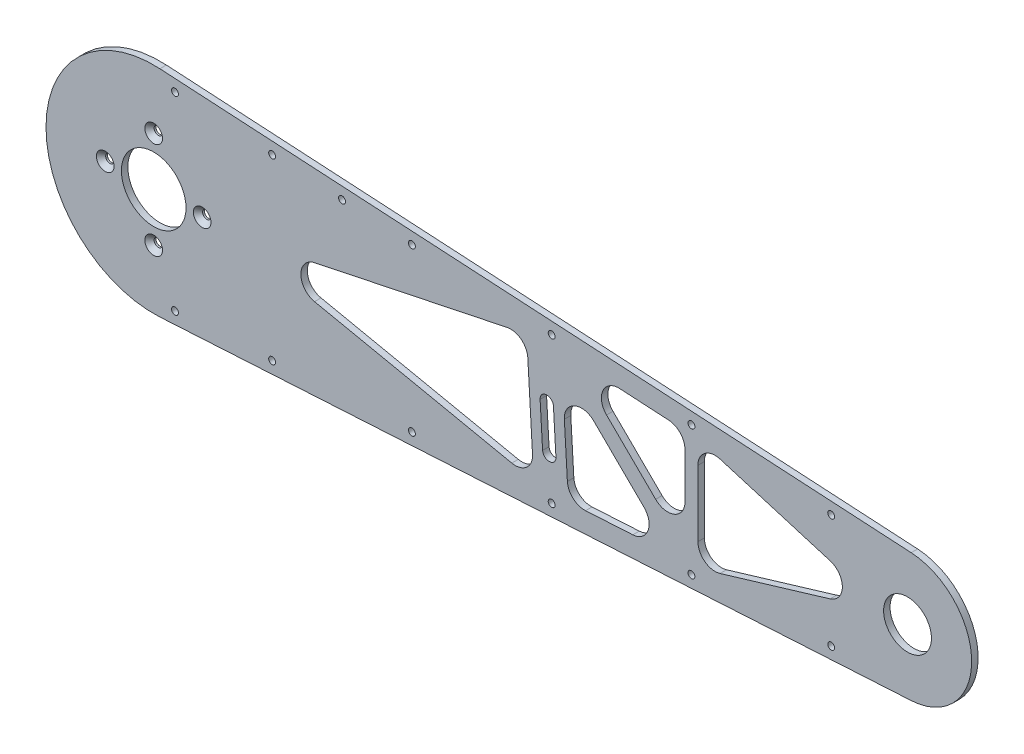
SolidWorks part; units mm, degrees
material "Thornel VCB-20 Carbon Cloth"
ref_plane "Front Plane" through (0, 0, 0) normal (0, 0, 1) x (1, 0, 0)
ref_plane "Top Plane" through (0, 0, 0) normal (0, 1, 0) x (1, 0, 0)
ref_plane "Right Plane" through (0, 0, 0) normal (1, 0, 0) x (0, 0, -1)
sketch "Sketch1" plane through (0, 0, 0) normal (0, 0, 1) x (1, 0, 0)
  line L0 (-175, 0) -> (175, 0) construction
  line L1 (-172.1122, 49.9165) -> (176.7203, 29.7354)
  line L2 (-172.1122, -49.9165) -> (176.7203, -29.7354)
  line L3 (139.566, 26.3757) -> (-120, 41.3925) construction
  line L4 (-55.1085, -37.6383) -> (9.783, -33.8841) construction
  line L5 (-125, 0) -> (-125, 62.9978) construction
  line L6 (-55.5713, 29.6383) -> (-120.4628, 33.3925) construction
  line L7 (-120.4628, 33.3925) -> (-120, 41.3925) construction
  line L8 (-55.5713, 29.6383) -> (-55.1085, 37.6383) construction
  line L9 (-88.0171, 31.5154) -> (-87.5543, 39.5154) construction
  line L10 (-120, -41.3925) -> (-165.1122, -44.0024) construction
  circle A0 centre (175, 0) radius 11.1125
  arc A1 (176.7203, 29.7354) -> (176.7203, -29.7354) centre (175, 0) cw
  circle A3 centre (-175, 0) radius 22.5 construction
  circle A7 centre (-175, 0) radius 15
  circle A9 centre (-120, 41.3925) radius 1.6
  circle A10 centre (-55.1085, 37.6383) radius 1.6
  circle A11 centre (9.783, 33.8841) radius 1.6
  circle A12 centre (74.6745, 30.1299) radius 1.6
  circle A13 centre (139.566, 26.3757) radius 1.6
  circle A15 centre (139.566, -26.3757) radius 1.6
  circle A16 centre (74.6745, -30.1299) radius 1.6
  circle A17 centre (9.783, -33.8841) radius 1.6
  circle A18 centre (-55.1085, -37.6383) radius 1.6
  circle A19 centre (-120, -41.3925) radius 1.6
  arc A20 (-172.1122, 49.9165) -> (-172.1122, -49.9165) centre (-175, 0) ccw
  circle A21 centre (-87.5543, 39.5154) radius 1.6
  circle A22 centre (-165.1122, -44.0024) radius 1.6
  circle A23 centre (-165.1122, 44.0024) radius 1.6
  point P4 (0, 0)
  point P18 (-175, 22.5)
  point P21 (-197.5, 0)
  point P22 (-175, -22.5)
  point P23 (-152.5, 0)
  point P30 (-88.0171, 31.5154)
  point P40 (-165.6042, -44.0308)
  dimension "D2" = 22.225
  dimension "D3" = 50
  dimension "D5" = 45
  dimension "D6" = 3.2
  dimension "D7" = 260
  dimension "D8" = 5
  dimension "D9" = 7
  dimension "D10" = 30
  dimension "D16" = 5
  dimension "D1" = 350
  dimension "D4" = 8
  dimension "D12" = 5.5
extrude "Boss-Extrude1" add sketch "Sketch1" along normal blind 3
sketch "Sketch4" plane through (0, 0, 3) normal (0, 0, 1) x (1, 0, 0)
  point P10 (-197.5, 0)
  point P13 (-175, 22.5)
  point P16 (-152.5, 0)
  point P19 (-175, -22.5)
hole_wizard "CSK for M3.5 Flat Head Machine Screw1" positions "Sketch4" profile "Sketch6" countersink size "M3.5" standard "ANSI Metric" end condition up to next
sketch "Sketch6" plane through (-197.5, 0, 3) normal (1, 0, 0) x (0, -1, 0)
  line L0 (0, 0) -> (0, 3)
  line L1 (0, 3) -> (1.95, 3)
  line L2 (1.95, 3) -> (1.95, 2.15)
  line L3 (1.95, 2.15) -> (4.1, 0)
  line L5 (4.1, 0) -> (0, 0)
  line L6 (-1.95, 2.15) -> (-4.1, 0) construction
  line L11 (0, -6.35) -> (0, 107.95) construction
  dimension "Thru Hole Dia." = 3.9
  dimension "Thru Hole Depth" = 3
  dimension "Near C'Sink Dia." = 8.2
  dimension "Near C'Sink Angle" = 90
sketch "Sketch7" plane through (0, 0, 3) normal (0, 0, 1) x (1, 0, 0)
  line L0 (74.6745, 30.1299) -> (74.6745, -30.1299) construction
  line L1 (74.6745, -30.1299) -> (175, 0) construction
  line L2 (175, 0) -> (74.6745, 30.1299) construction
  line L3 (175, 0) -> (-152.5, 0) construction
  line L4 (175, -29.8349) -> (175, 29.8349) construction
  line L5 (87.9755, 23.0029) -> (139.0575, 7.6619)
  line L6 (139.0575, -7.6619) -> (87.9755, -23.0029)
  line L7 (77.6745, -15.341) -> (77.6745, 15.341)
  line L8 (9.783, -33.8841) -> (5.5294, 39.6394) construction
  line L9 (9.783, 33.8841) -> (74.6745, -30.1299) construction
  line L10 (9.783, 33.8841) -> (74.6745, 30.1299) construction
  line L11 (9.783, -33.8841) -> (74.6745, -30.1299) construction
  line L12 (-152.5, 0) -> (-55.1085, 37.6383) construction
  line L13 (-55.1085, 37.6383) -> (9.783, 33.8841) construction
  line L14 (9.783, 33.8841) -> (-152.5, 0) construction
  line L15 (71.6745, -2.4224) -> (71.6745, 18.7462)
  line L16 (64.1365, 26.7329) -> (41.3408, 28.0517)
  line L17 (35.2605, 14.3698) -> (58.0563, -8.1177)
  line L18 (29.2743, 9.0376) -> (52.6422, -14.0143)
  line L19 (47.486, -27.6962) -> (25.5253, -28.9667)
  line L20 (17.0766, -21.4421) -> (15.6694, 2.8804)
  line L21 (176.7203, 29.7354) -> (-172.1122, 49.9165) construction
  line L22 (-172.1122, -49.9165) -> (176.7203, -29.7354) construction
  line L23 (0.8889, -18.6602) -> (-1.2973, 19.1278)
  line L24 (-10.9191, 26.4969) -> (-100.3161, 7.8311)
  line L25 (-100.3161, -7.8311) -> (-8.7329, -26.9534)
  line L35 (-197.5, 0) -> (-55.1085, 37.6383) construction
  line L52 (-55.1085, -37.6383) -> (-175, -22.5) construction
  line L53 (-15.2425, -47.7117) -> (-52.5586, -43) construction
  line L54 (-0.7058, -39.4678) -> (2.1851, -39.8329) construction
  line L55 (8.6627, -14.5198) -> (7.5076, 5.4468) construction
  line L56 (5.5679, -14.6989) -> (4.4127, 5.2678)
  line L57 (11.7575, -14.3408) -> (10.6024, 5.6258)
  line L58 (176.7203, 29.7354) -> (-172.1122, 49.9165) construction
  arc A0 (139.0575, 7.6619) -> (139.0575, -7.6619) centre (136.7565, 0) cw
  arc A1 (87.9755, -23.0029) -> (77.6745, -15.341) centre (85.6745, -15.341) cw
  arc A2 (87.9755, 23.0029) -> (77.6745, 15.341) centre (85.6745, 15.341) ccw
  arc A3 (71.6745, 18.7462) -> (64.1365, 26.7329) centre (63.6745, 18.7462) ccw
  arc A4 (41.3408, 28.0517) -> (35.2605, 14.3698) centre (40.8787, 20.065) ccw
  arc A5 (71.6745, -2.4224) -> (58.0563, -8.1177) centre (63.6745, -2.4224) cw
  arc A6 (52.6422, -14.0143) -> (47.486, -27.6962) centre (47.024, -19.7095) cw
  arc A7 (25.5253, -28.9667) -> (17.0766, -21.4421) centre (25.0632, -20.98) cw
  arc A8 (29.2743, 9.0376) -> (15.6694, 2.8804) centre (23.6561, 3.3424) ccw
  arc A9 (0.8889, -18.6602) -> (-8.7329, -26.9534) centre (-7.0978, -19.1222) cw
  arc A10 (-1.2973, 19.1278) -> (-10.9191, 26.4969) centre (-9.2839, 18.6658) ccw
  arc A11 (-100.3161, 7.8311) -> (-100.3161, -7.8311) centre (-98.681, 0) ccw
  circle A30 centre (-175, 0) radius 15 construction
  circle A31 centre (-175, 0) radius 15 construction
  circle A32 centre (-175, 0) radius 22.5 construction
  circle A49 centre (9.783, -33.8841) radius 1.6 construction
  circle A50 centre (9.783, -33.8841) radius 1.6
  circle A52 centre (175, 0) radius 11.1125 construction
  circle A53 centre (175, 0) radius 11.1125 construction
  arc A56 (5.5679, -14.6989) -> (11.7575, -14.3408) centre (8.6627, -14.5198) ccw
  arc A57 (10.6024, 5.6258) -> (4.4127, 5.2678) centre (7.5076, 5.4468) ccw
  point P3 (70.0442, -0.8142)
  point P26 (175, 0)
  point P28 (175, 0)
  point P36 (164.5699, 0)
  point P59 (-137.8221, 0)
  point P63 (175, 29.8349)
  point P102 (-15.2425, -47.7117)
  point P126 (8.0851, -4.5365)
  dimension "D8" = 8
  dimension "D12" = 5
  dimension "D20" = 3.1
  dimension "D1" = 3
  dimension "D3" = 8
  dimension "D4" = 8
  dimension "D5" = 8
  dimension "D6" = 16
  dimension "D7" = 6
  dimension "D9" = 6
  dimension "D14" = 5
  dimension "D16" = 24.8967
  dimension "D22" = 20
extrude "Cut-Extrude1" cut sketch "Sketch7" against normal blind 10 contours L57 A57 L56 A56 | L24 A11 L25 A9 L23 A10 | L18 A8 L20 A7 L19 A6 | L20 A8 L18 A6 L19 A7 | L17 A5 L15 A3 L16 A4 | L7 A2 L5 A0 L6 A1 region at (32.1755, -11.823, 3) region at (-42.4165, -0.2065, 3) region at (8.0851, -4.5365, 3)
sketch "Sketch9" [suppressed] plane through (0, 0, 3) normal (0, 0, 1) x (1, 0, 0)
  line L2 (176.7203, 29.7354) -> (-172.1122, 49.9165) construction
  line L3 (-172.1122, -49.9165) -> (176.7203, -29.7354) construction
  line L4 (254.5375, 0) -> (208, 0) construction
  line L5 (200.557, 2) -> (203.931, 2)
  line L6 (200.557, -2) -> (203.931, -2)
  line L7 (162.9445, 26.3755) -> (155.7345, 26.7926)
  line L8 (162.9445, -26.3755) -> (155.7345, -26.7926)
  arc A1 (155.7345, -26.7926) -> (155.7345, 26.7926) centre (175, 0) ccw
  arc A2 (176.7203, -29.7354) -> (176.7203, 29.7354) centre (175, 0) ccw construction
  arc A3 (200.557, -2) -> (200.557, 2) centre (175, 0) ccw
  arc A4 (162.9445, 26.3755) -> (203.931, 2) centre (175, 0) cw
  arc A5 (203.931, -2) -> (162.9445, -26.3755) centre (175, 0) cw
  dimension "D1" = 33
  dimension "D2" = 4
  dimension "D3" = 4
extrude "Boss-Extrude2" [suppressed] add sketch "Sketch9" against normal up to surface (3 mm away) up to face at (-37.2203, -0.0266, 0)
fillet "Fillet1" [suppressed] radius 1
fillet "Fillet2" [suppressed] radius 80
